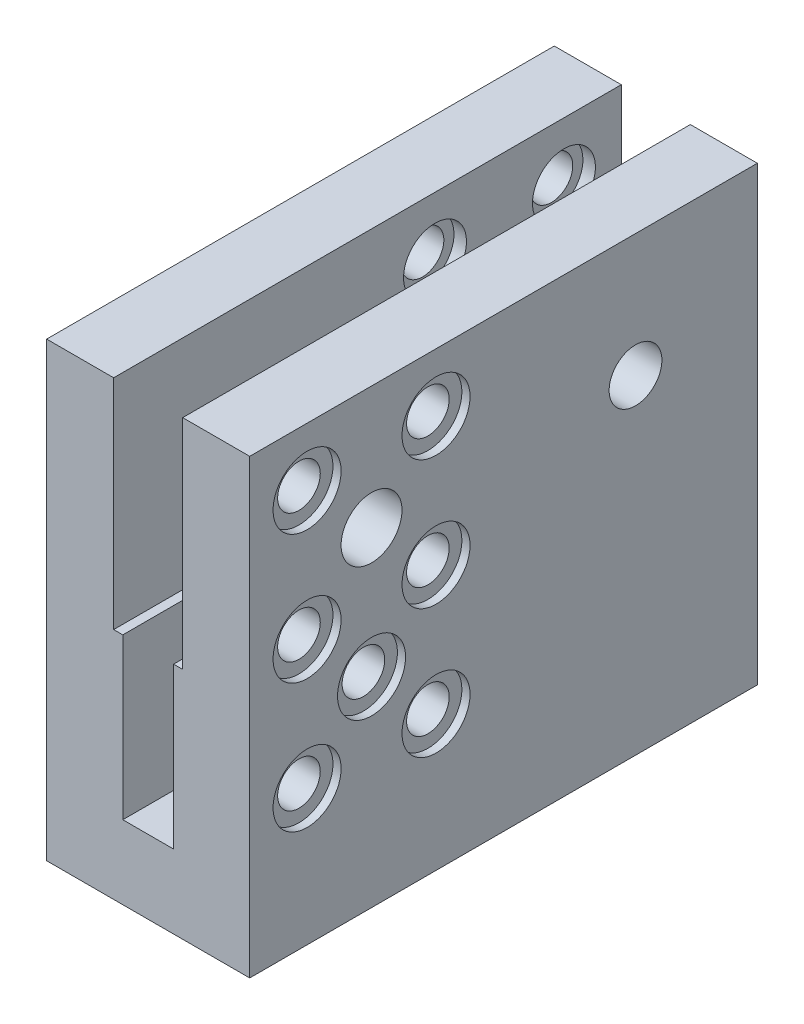
SolidWorks part; units mm, degrees
ref_plane "Front Plane" through (0, 0, 0) normal (0, 0, 1) x (1, 0, 0)
ref_plane "Top Plane" through (0, 0, 0) normal (0, 1, 0) x (1, 0, 0)
ref_plane "Right Plane" through (0, 0, 0) normal (1, 0, 0) x (0, 0, -1)
sketch "Sketch2" plane through (0, 0, 0) normal (0, 1, 0) x (1, 0, 0)
  line L1 (-10, 25) -> (10, 25)
  line L2 (-10, 25) -> (-10, -25)
  line L3 (-10, -25) -> (10, -25)
  line L4 (10, 25) -> (10, -25)
  line L5 (-10, 25) -> (10, -25) construction
  line L6 (-10, -25) -> (10, 25) construction
  point P1 (0, 0)
  dimension "D1" = 20
  dimension "D2" = 50
extrude "Boss-Extrude1" add sketch "Sketch2" along normal blind 44.5
sketch "Sketch3" plane through (0, 0, 25) normal (0, 0, 1) x (1, 0, 0)
  line L0 (-10, 44.5) -> (10, 44.5) construction
  line L1 (-3.4, 44.5) -> (3.4, 44.5)
  line L2 (-3.4, 44.5) -> (-3.4, 23.02)
  line L3 (-3.4, 23.02) -> (3.4, 23.02)
  line L4 (3.4, 44.5) -> (3.4, 23.02)
  line L7 (-2.5, 7.25) -> (2.5, 7.25)
  line L8 (-2.5, 7.25) -> (-2.5, 23.02)
  line L9 (-2.5, 23.02) -> (2.5, 23.02)
  line L10 (2.5, 7.25) -> (2.5, 23.02)
  point P8 (0, 23.02)
  point P12 (0, 23.02)
  dimension "D1" = 6.8
  dimension "D2" = 21.48
  dimension "D3" = 5
  dimension "D4" = 15.77
extrude "Cut-Extrude3" cut sketch "Sketch3" against normal through all contours L10 L9 L8 L7 | L2 L3 L4 L1
sketch "Sketch4" plane through (10, 0, 0) normal (1, 0, 0) x (0, 0, -1)
  line L0 (-25, 0) -> (25, 0) construction
  line L1 (-25, 44.5) -> (-25, 23.02) construction
  line L2 (-13, 32.41) -> (-13, -2.0434) construction
  line L3 (-6.65, 38.76) -> (-6.65, -2.0434) construction
  circle A0 centre (-13, 32.41) radius 3
  circle A7 centre (-13, 19.71) radius 2.1
  circle A9 centre (-6.65, 38.76) radius 2.1
  circle A10 centre (-6.65, 26.06) radius 2.1
  circle A11 centre (-6.65, 13.36) radius 2.1
  circle A14 centre (-19.35, 13.36) radius 2.1
  circle A15 centre (-19.35, 26.06) radius 2.1
  circle A16 centre (-19.35, 38.76) radius 2.1
  dimension "D3" = 6
  dimension "D6" = 4.2
  dimension "D10" = 4.2
  dimension "D11" = 4.2
  dimension "D12" = 4.2
  dimension "D1" = 32.41
  dimension "D2" = 12
  dimension "D4" = 12.7
  dimension "D8" = 6.35
  dimension "D9" = 6.35
  dimension "D13" = 12.7
  dimension "D14" = 12.7
extrude "Cut-Extrude4" cut sketch "Sketch4" against normal through all contours A0
extrude "Cut-Extrude5" cut sketch "Sketch4<3>" against normal blind 6.6 contours A10 | A9 | A14 | A11 | A15 | A16 | A7
sketch "Sketch4<3>" plane through (10, 0, 0) normal (1, 0, 0) x (0, 0, -1) same geometry as "Sketch4"
sketch "Sketch5" plane through (-10, 0, 0) normal (-1, 0, 0) x (0, 0, 1)
  circle A0 centre (13, 32.41) radius 2.6
  circle A1 centre (13, 32.41) radius 3
  dimension "D1" = 5.2
  dimension "D2" = 6
extrude "Boss-Extrude2" add sketch "Sketch5" against normal blind 6.6
sketch "Sketch6" plane through (3.4, 0, 0) normal (-1, 0, 0) x (0, 0, 1)
  circle A2 centre (6.65, 13.36) radius 3.1
  circle A3 centre (6.65, 26.06) radius 3.1
  circle A4 centre (13, 19.71) radius 3.1
  circle A5 centre (19.35, 13.36) radius 3.1
  circle A6 centre (19.35, 26.06) radius 3.1
  circle A7 centre (19.35, 38.76) radius 3.1
  circle A8 centre (6.65, 38.76) radius 3.1
  dimension "D1" = 6.2
extrude "Cut-Extrude6" cut sketch "Sketch6" against normal blind 1.23
fillet "Fillet1" [suppressed] radius 0.5
sketch "Sketch8" plane through (10, 0, 0) normal (1, 0, 0) x (0, 0, -1)
  circle A0 centre (-6.65, 38.76) radius 3.35
  circle A1 centre (-6.65, 26.06) radius 3.35
  circle A2 centre (-6.65, 13.36) radius 3.35
  circle A4 centre (-13, 19.71) radius 3.35
  circle A5 centre (-19.35, 38.76) radius 3.35
  circle A6 centre (-19.35, 26.06) radius 3.35
  circle A7 centre (-19.35, 13.36) radius 3.35
  dimension "D1" = 6.7
extrude "Cut-Extrude8" cut sketch "Sketch8" against normal blind 0.8
sketch "Sketch9" plane through (10, 0, 0) normal (1, 0, 0) x (0, 0, -1)
  line L0 (0, 44.5) -> (0, 0) construction
  line L1 (-25, 44.5) -> (25, 44.5) construction
ref_plane "Plane1" through (0, 0, 0) normal (0, 0, -1) x (-1, 0, 0)
sketch "Sketch10" plane through (0, 0, -25) normal (0, 0, -1) x (-1, 0, 0)
  line L0 (0, 7.25) -> (0, 0) construction
  line L1 (2.5, 7.25) -> (-2.5, 7.25) construction
ref_plane "Plane2" through (0, 0, 0) normal (1, 0, 0) x (0, 0, -1)
sketch "Sketch11" plane through (0, 0, 0) normal (1, 0, 0) x (0, 0, -1)
  line L0 (0, 44.5) -> (0, 0) construction
pattern_circular "CirPattern1" count 2 over 180 about axis through (0, 44.5, 0) along (0, -1, 0) of "Cut-Extrude8", "Cut-Extrude6", "Boss-Extrude2", "Cut-Extrude5", "Cut-Extrude4"
sketch "Sketch12" plane through (-10, 0, 0) normal (1, 0, 0) x (0, 0, -1)
  line L0 (-13, 32.41) -> (-13, 6.59) construction
  circle A0 centre (-13, 6.59) radius 2.35
  circle A2 centre (-13, 32.41) radius 2.6 construction
  point P2 (0, 0)
  dimension "D1" = 4.7
  dimension "D2" = 25.82
extrude "Cut-Extrude9" cut sketch "Sketch12" along normal blind 6.6
